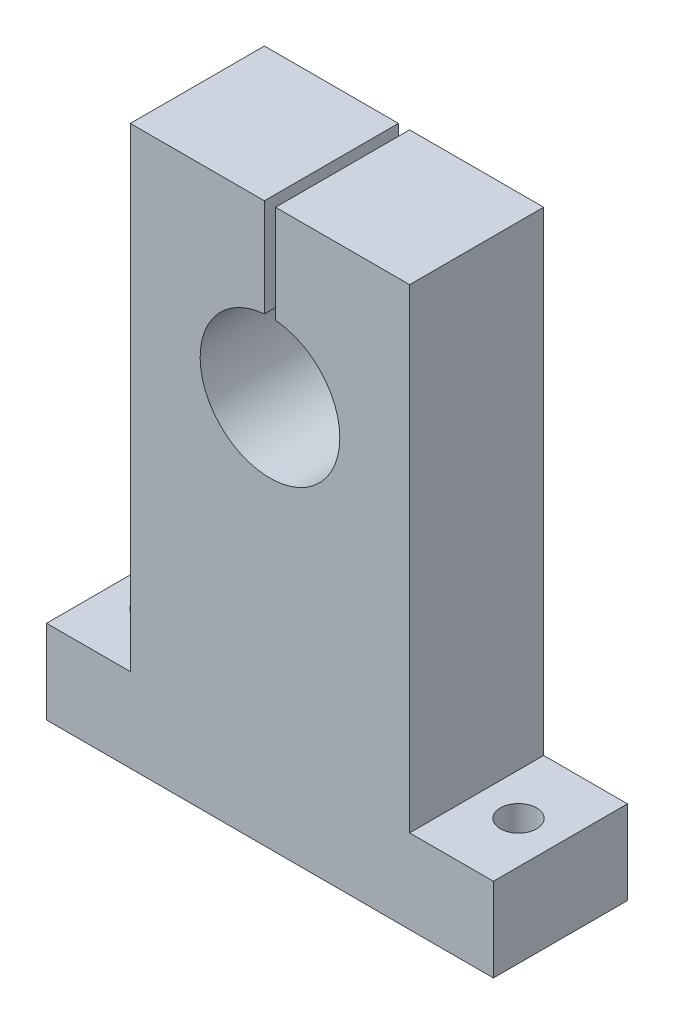
SolidWorks part; units mm, degrees
material "AISI 304"
ref_plane "Спереди" through (0, 0, 0) normal (0, 0, 1) x (1, 0, 0)
ref_plane "Сверху" through (0, 0, 0) normal (0, 1, 0) x (1, 0, 0)
ref_plane "Справа" through (0, 0, 0) normal (1, 0, 0) x (0, 0, -1)
ref_axis "ОсьX" through (-88.99, 0, 0) along (1, 0, 0)
ref_axis "ОсьZ" through (0, 55, 0) along (0, -1, 0)
ref_axis "ОсьY" through (0, 0, -88.99) along (0, 0, 1)
sketch "Эскиз1" plane through (0, 0, 0) normal (0, 0, 1) x (1, 0, 0)
  line L0 (-40, -70) -> (40, -70)
  line L1 (40, -70) -> (40, -55)
  line L2 (40, -55) -> (25, -55)
  line L3 (25, -55) -> (25, 30)
  line L4 (25, 30) -> (1, 30)
  line L5 (-25, 30) -> (-25, -55)
  line L6 (-25, -55) -> (-40, -55)
  line L7 (-40, -55) -> (-40, -70)
  line L8 (-1, 30) -> (-25, 30)
  line L10 (-1, 30) -> (-1, 12.4599)
  line L12 (1, 30) -> (1, 12.4599)
  line L13 (0, 0) -> (0, 9.6817) construction
  arc A0 (-1, 12.4599) -> (1, 12.4599) centre (0, 0) ccw
  dimension "D1" = 25
  dimension "D4" = 70
  dimension "D2" = 80
  dimension "D3" = 15
  dimension "D5" = 50
  dimension "D6" = 100
  dimension "D7" = 2
extrude "Бобышка-Вытянуть1" add sketch "Эскиз1" along normal mid plane 24
sketch "Эскиз2" plane through (0, -55, 0) normal (0, 1, 0) x (1, 0, 0)
  line L0 (0, 22.2258) -> (0, -20.5967) construction
  circle A0 centre (-32.5, 0) radius 3.25
  circle A1 centre (32.5, 0) radius 3.25
  dimension "D1" = 65
  dimension "D2" = 6.5
extrude "Вырез-Вытянуть1" cut sketch "Эскиз2" against normal through all
